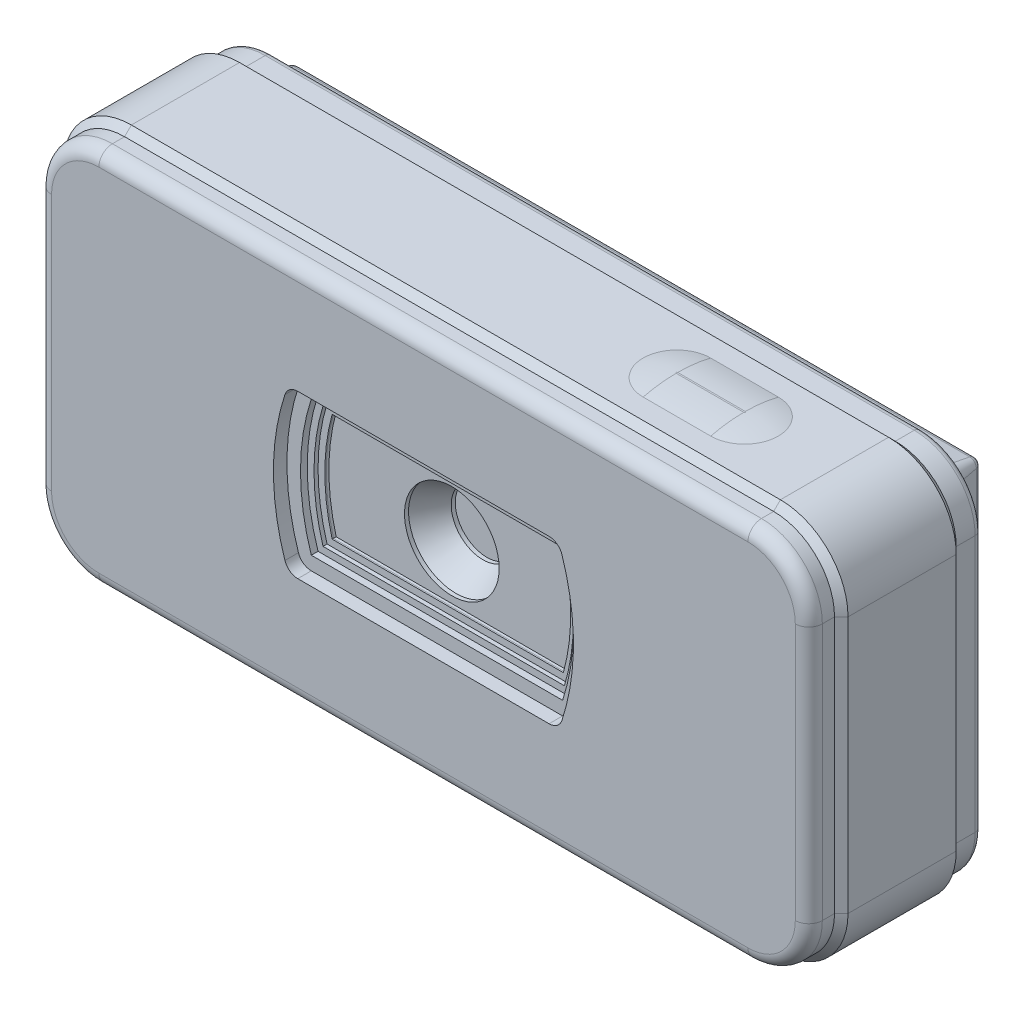
SolidWorks part; units mm, degrees
ref_plane "정면" through (0, 0, 0) normal (0, 0, 1) x (1, 0, 0)
ref_plane "윗면" through (0, 0, 0) normal (0, 1, 0) x (1, 0, 0)
ref_plane "우측면" through (0, 0, 0) normal (1, 0, 0) x (0, 0, -1)
sketch "스케치1" plane through (0, 0, 0) normal (0, 0, 1) x (1, 0, 0)
  line L1 (-29, -14.5) -> (29, -14.5)
  line L2 (-29, -14.5) -> (-29, 14.5)
  line L3 (-29, 14.5) -> (29, 14.5)
  line L4 (29, -14.5) -> (29, 14.5)
  line L5 (-29, -14.5) -> (29, 14.5) construction
  line L6 (-29, 14.5) -> (29, -14.5) construction
  point P0 (0, 0)
  dimension "D1" = 29
  dimension "D2" = 58
extrude "보스-돌출1" add sketch "스케치1" along normal blind 9
fillet "필렛1" radius 5 4 edges at (-29, -14.5, 4.5) (29, -14.5, 4.5) (29, 14.5, 4.5) (-29, 14.5, 4.5)
chamfer "모따기1" distance 0.5 angle 45 16 edges at (27.5355, -13.0355, 0) (29, 0, 0) (27.5355, 13.0355, 0) (0, 14.5, 0) (-27.5355, 13.0355, 0) (-29, 0, 0) (-27.5355, -13.0355, 0) (0, -14.5, 0) (-27.5355, 13.0355, 9) (0, 14.5, 9) (27.5355, 13.0355, 9) (29, 0, 9) (27.5355, -13.0355, 9) (0, -14.5, 9) (-27.5355, -13.0355, 9) (-29, 0, 9)
sketch "스케치2" plane through (0, 0, 9) normal (0, 0, 1) x (1, 0, 0)
  line L4 (24, 14) -> (-24, 14)
  line L5 (-28.5, 9.5) -> (-28.5, -9.5)
  line L6 (-24, -14) -> (24, -14)
  line L7 (28.5, -9.5) -> (28.5, 9.5)
  line L8 (24, 14) -> (-24, 14)
  line L9 (-28.5, 9.5) -> (-28.5, -9.5)
  line L10 (-24, -14) -> (24, -14)
  line L11 (28.5, -9.5) -> (28.5, 9.5)
  arc A4 (-24, 14) -> (-28.5, 9.5) centre (-24, 9.5) ccw
  arc A5 (-28.5, -9.5) -> (-24, -14) centre (-24, -9.5) ccw
  arc A6 (24, -14) -> (28.5, -9.5) centre (24, -9.5) ccw
  arc A7 (28.5, 9.5) -> (24, 14) centre (24, 9.5) ccw
  arc A8 (-24, 14) -> (-28.5, 9.5) centre (-24, 9.5) ccw
  arc A9 (-28.5, -9.5) -> (-24, -14) centre (-24, -9.5) ccw
  arc A10 (24, -14) -> (28.5, -9.5) centre (24, -9.5) ccw
  arc A11 (28.5, 9.5) -> (24, 14) centre (24, 9.5) ccw
  dimension "D1" = 0
extrude "보스-돌출2" add sketch "스케치2" along normal blind 1.9 separate body
fillet "필렛2" radius 1 8 edges at (28.5, 0, 10.9) (27.182, -12.682, 10.9) (0, -14, 10.9) (-27.182, -12.682, 10.9) (-28.5, 0, 10.9) (-27.182, 12.682, 10.9) (0, 14, 10.9) (27.182, 12.682, 10.9)
sketch "스케치3" plane through (0, 0, 0) normal (0, 0, -1) x (-1, 0, 0)
  line L4 (-28.5, 9.5) -> (-28.5, -9.5)
  line L5 (-24, -14) -> (24, -14)
  line L6 (28.5, -9.5) -> (28.5, 9.5)
  line L7 (24, 14) -> (-24, 14)
  line L8 (-28.5, 9.5) -> (-28.5, -9.5)
  line L9 (-24, -14) -> (24, -14)
  line L10 (28.5, -9.5) -> (28.5, 9.5)
  line L11 (24, 14) -> (-24, 14)
  arc A4 (-28.5, -9.5) -> (-24, -14) centre (-24, -9.5) ccw
  arc A5 (24, -14) -> (28.5, -9.5) centre (24, -9.5) ccw
  arc A6 (28.5, 9.5) -> (24, 14) centre (24, 9.5) ccw
  arc A7 (-24, 14) -> (-28.5, 9.5) centre (-24, 9.5) ccw
  arc A8 (-28.5, -9.5) -> (-24, -14) centre (-24, -9.5) ccw
  arc A9 (24, -14) -> (28.5, -9.5) centre (24, -9.5) ccw
  arc A10 (28.5, 9.5) -> (24, 14) centre (24, 9.5) ccw
  arc A11 (-24, 14) -> (-28.5, 9.5) centre (-24, 9.5) ccw
  dimension "D1" = 0
extrude "보스-돌출3" add sketch "스케치3" along normal blind 1.9 separate body
fillet "필렛3" radius 0.5 8 edges at (0, 14, -1.9) (-27.182, 12.682, -1.9) (-28.5, 0, -1.9) (-27.182, -12.682, -1.9) (0, -14, -1.9) (27.182, -12.682, -1.9) (28.5, 0, -1.9) (27.182, 12.682, -1.9)
sketch "스케치4" plane through (0, 0, -1.9) normal (0, 0, -1) x (-1, 0, 0)
  line L1 (-25, -11.75) -> (25, -11.75)
  line L2 (-26, -10.75) -> (-26, 10.75)
  line L3 (-25, 11.75) -> (25, 11.75)
  line L4 (26, -10.75) -> (26, 10.75)
  line L5 (-26, -11.75) -> (26, 11.75) construction
  line L6 (-26, 11.75) -> (26, -11.75) construction
  arc A0 (25, 11.75) -> (26, 10.75) centre (25, 10.75) cw
  arc A1 (25, -11.75) -> (26, -10.75) centre (25, -10.75) ccw
  arc A2 (-25, -11.75) -> (-26, -10.75) centre (-25, -10.75) cw
  arc A3 (-26, 10.75) -> (-25, 11.75) centre (-25, 10.75) cw
  point P0 (0, 0)
  dimension "D3" = 1
  dimension "D1" = 23.5
  dimension "D2" = 52
extrude "보스-돌출4" add sketch "스케치4" along normal blind 3 draft 11
fillet "필렛4" radius 0.5 8 edges at (-25.4169, 0, -4.9) (-25.2948, -11.0448, -4.9) (0, -11.1669, -4.9) (25.2948, -11.0448, -4.9) (25.4169, 0, -4.9) (25.2948, 11.0448, -4.9) (0, 11.1669, -4.9) (-25.2948, 11.0448, -4.9)
sketch "스케치5" plane through (0, 0, 10.9) normal (0, 0, 1) x (1, 0, 0)
  line L0 (0, 0) -> (8.2211, 0) construction
  line L1 (-9.2922, -6) -> (9.2922, -6)
  line L3 (-9.2922, 6) -> (9.2922, 6)
  line L4 (0, 0) -> (0, 4.2053) construction
  line L5 (-10, -6) -> (10, 6) construction
  line L6 (-10, 6) -> (10, -6) construction
  arc A0 (10.2423, -5.3119) -> (10.2423, 5.3119) centre (-5.9384, 0) ccw
  arc A1 (-10.2423, -5.3119) -> (-10.2423, 5.3119) centre (5.9384, 0) cw
  arc A2 (9.2922, 6) -> (10.2423, 5.3119) centre (9.2922, 5) cw
  arc A3 (9.2922, -6) -> (10.2423, -5.3119) centre (9.2922, -5) ccw
  arc A4 (-9.2922, -6) -> (-10.2423, -5.3119) centre (-9.2922, -5) cw
  arc A5 (-10.2423, 5.3119) -> (-9.2922, 6) centre (-9.2922, 5) cw
  point P0 (0, 0)
  dimension "D3" = 1
  dimension "D1" = 20
  dimension "D2" = 12
extrude "컷-돌출1" cut sketch "스케치5" against normal blind 1
sketch "스케치6" plane through (0, 0, 9.9) normal (0, 0, 1) x (1, 0, 0)
  line L0 (9.2922, 5) -> (-9.2922, 5)
  line L1 (-9.2922, -5) -> (9.2922, -5)
  line L2 (9.2922, 6) -> (-9.2922, 6)
  line L3 (-9.2922, -6) -> (9.2922, -6)
  line L4 (9.2922, 6) -> (-9.2922, 6) construction
  line L5 (-9.2922, -6) -> (9.2922, -6) construction
  arc A0 (-9.2922, 5) -> (-9.2922, 5) centre (-9.2922, 5) ccw
  arc A1 (-9.2922, 5) -> (-9.2922, -5) centre (5.9384, 0) ccw
  arc A2 (-9.2922, -5) -> (-9.2922, -5) centre (-9.2922, -5) ccw
  arc A3 (9.2922, -5) -> (9.2922, -5) centre (9.2922, -5) ccw
  arc A4 (9.2922, -5) -> (9.2922, 5) centre (-5.9384, 0) ccw
  arc A5 (9.2922, 5) -> (9.2922, 5) centre (9.2922, 5) ccw
  arc A6 (10.2423, 5.3119) -> (9.2922, 6) centre (9.2922, 5) ccw
  arc A7 (-9.2922, 6) -> (-10.2423, 5.3119) centre (-9.2922, 5) ccw
  arc A8 (-10.2423, 5.3119) -> (-10.2423, -5.3119) centre (5.9384, 0) ccw
  arc A9 (-10.2423, -5.3119) -> (-9.2922, -6) centre (-9.2922, -5) ccw
  arc A10 (9.2922, -6) -> (10.2423, -5.3119) centre (9.2922, -5) ccw
  arc A11 (10.2423, -5.3119) -> (10.2423, 5.3119) centre (-5.9384, 0) ccw
  arc A12 (10.2423, 5.3119) -> (9.2922, 6) centre (9.2922, 5) ccw construction
  arc A13 (-9.2922, 6) -> (-10.2423, 5.3119) centre (-9.2922, 5) ccw construction
  arc A14 (-10.2423, 5.3119) -> (-10.2423, -5.3119) centre (5.9384, 0) ccw construction
  arc A15 (-10.2423, -5.3119) -> (-9.2922, -6) centre (-9.2922, -5) ccw construction
  arc A16 (9.2922, -6) -> (10.2423, -5.3119) centre (9.2922, -5) ccw construction
  arc A17 (10.2423, -5.3119) -> (10.2423, 5.3119) centre (-5.9384, 0) ccw construction
  dimension "D1" = 0
  dimension "D2" = 1
extrude "컷-돌출2" cut sketch "스케치6" against normal blind 0.5
sketch "스케치7" plane through (0, 0, 9.4) normal (0, 0, 1) x (1, 0, 0)
  line L0 (8.9257, 4.5) -> (-8.9257, 4.5)
  line L1 (-8.9257, -4.5) -> (8.9257, -4.5)
  line L2 (9.2922, 5) -> (-9.2922, 5)
  line L3 (-9.2922, -5) -> (9.2922, -5)
  line L4 (9.2922, 5) -> (-9.2922, 5) construction
  line L5 (-9.2922, -5) -> (9.2922, -5) construction
  arc A0 (-8.9257, 4.5) -> (-8.9257, -4.5) centre (5.9384, 0) ccw
  arc A1 (8.9257, -4.5) -> (8.9257, 4.5) centre (-5.9384, 0) ccw
  arc A2 (9.2922, -5) -> (9.2922, 5) centre (-5.9384, 0) ccw
  arc A3 (-9.2922, 5) -> (-9.2922, -5) centre (5.9384, 0) ccw
  arc A4 (9.2922, -5) -> (9.2922, 5) centre (-5.9384, 0) ccw construction
  arc A5 (-9.2922, 5) -> (-9.2922, -5) centre (5.9384, 0) ccw construction
  dimension "D1" = 0
  dimension "D2" = 0.5
extrude "컷-돌출3" cut sketch "스케치7" against normal blind 0.3
sketch "스케치8" plane through (0, 0, 9.1) normal (0, 0, 1) x (1, 0, 0)
  line L0 (8.5499, 4) -> (-8.5499, 4)
  line L1 (-8.5499, -4) -> (8.5499, -4)
  line L2 (8.9257, 4.5) -> (-8.9257, 4.5)
  line L3 (-8.9257, -4.5) -> (8.9257, -4.5)
  line L4 (8.9257, 4.5) -> (-8.9257, 4.5) construction
  line L5 (-8.9257, -4.5) -> (8.9257, -4.5) construction
  arc A0 (-8.5499, 4) -> (-8.5499, -4) centre (5.9384, 0) ccw
  arc A1 (8.5499, -4) -> (8.5499, 4) centre (-5.9384, 0) ccw
  arc A2 (8.9257, -4.5) -> (8.9257, 4.5) centre (-5.9384, 0) ccw
  arc A3 (-8.9257, 4.5) -> (-8.9257, -4.5) centre (5.9384, 0) ccw
  arc A4 (8.9257, -4.5) -> (8.9257, 4.5) centre (-5.9384, 0) ccw construction
  arc A5 (-8.9257, 4.5) -> (-8.9257, -4.5) centre (5.9384, 0) ccw construction
  dimension "D1" = 0
  dimension "D2" = 0.5
extrude "컷-돌출4" cut sketch "스케치8" against normal blind 0.3
sketch "스케치9" plane through (0, 0, 8.8) normal (0, 0, 1) x (1, 0, 0)
  circle A0 centre (0, 0) radius 3.5
  dimension "D1" = 7
extrude "컷-돌출5" cut sketch "스케치9" against normal blind 0.3
sketch "스케치10" plane through (0, 0, 8.5) normal (0, 0, 1) x (1, 0, 0)
  circle A1 centre (0, 0) radius 3.5
  circle A2 centre (0, 0) radius 3.5
  dimension "D1" = 0
extrude "컷-돌출6" cut sketch "스케치10" against normal blind 2 draft 30
sketch "스케치11" plane through (0, 0, 6.5) normal (0, 0, 1) x (1, 0, 0)
  circle A1 centre (0, 0) radius 2.3453
  circle A2 centre (0, 0) radius 2.3453
  dimension "D1" = 0
extrude "컷-돌출7" cut sketch "스케치11" against normal blind 0.3
sketch "스케치12" plane through (0, 14.5, 0) normal (0, 1, 0) x (1, 0, 0)
  line L0 (-24, -0.5) -> (-24, -8.5) construction
  line L1 (-24, -0.5) -> (-24, -8.5) construction
  line L2 (-24, -4.5) -> (43.1915, -4.5) construction
  line L3 (12.3471, -4.5) -> (17.3471, -4.5) construction
  line L4 (12.3471, -2) -> (17.3471, -2)
  line L5 (12.3471, -7) -> (17.3471, -7)
  arc A0 (12.3471, -2) -> (12.3471, -7) centre (12.3471, -4.5) ccw
  arc A1 (17.3471, -7) -> (17.3471, -2) centre (17.3471, -4.5) ccw
  point P2 (-24, -4.5)
  point P7 (14.8471, -4.5)
  dimension "D1" = 2.5
  dimension "D2" = 5
extrude "보스-돌출5" add sketch "스케치12" along normal blind 0.3
fillet "필렛5" radius 10.1 4 edges at (14.8471, 14.8, 2) (19.8471, 14.8, 4.5) (14.8471, 14.8, 7) (9.8471, 14.8, 4.5)
